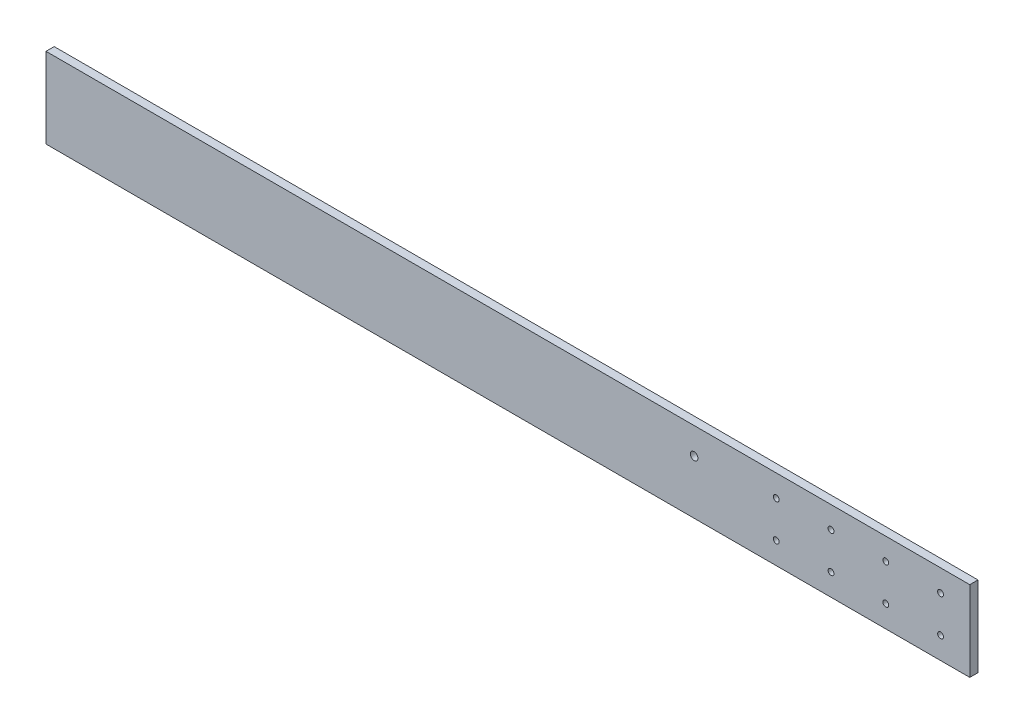
SolidWorks part; units mm, degrees
ref_plane "Front Plane" through (0, 0, 0) normal (0, 0, 1) x (1, 0, 0)
ref_plane "Top Plane" through (0, 0, 0) normal (0, 1, 0) x (1, 0, 0)
ref_plane "Right Plane" through (0, 0, 0) normal (1, 0, 0) x (0, 0, -1)
sketch "Sketch2" plane through (0, 0, 0) normal (0, 0, 1) x (1, 0, 0)
  line L0 (253, 0) -> (127, 0) construction
  line L1 (-253, -22) -> (253, -22)
  line L2 (-253, -22) -> (-253, 22)
  line L3 (-253, 22) -> (253, 22)
  line L4 (253, -22) -> (253, 22)
  line L5 (-253, -22) -> (253, 22) construction
  line L6 (-253, 22) -> (253, -22) construction
  line L7 (127, -1) -> (127, 9) construction
  line L8 (247, 3.3321) -> (247, 22) construction
  circle A0 centre (102, 7.5) radius 2.1 construction
  circle A1 centre (102, 7.5) radius 2.1
  circle A2 centre (237, 10) radius 1.6
  circle A3 centre (207, 10) radius 1.6
  circle A4 centre (177, 10) radius 1.6
  circle A5 centre (147, 10) radius 1.6
  circle A6 centre (207, -10) radius 1.6
  circle A7 centre (177, -10) radius 1.6
  circle A8 centre (147, -10) radius 1.6
  circle A9 centre (237, -10) radius 1.6
  point P0 (0, 0)
  dimension "D3" = 10
  dimension "D5" = 3.2
  dimension "D1" = 44
  dimension "D2" = 506
  dimension "D4" = 10
  dimension "D6" = 4
  dimension "D7" = 2
extrude "Boss-Extrude1" add sketch "Sketch2" along normal blind 4.5
